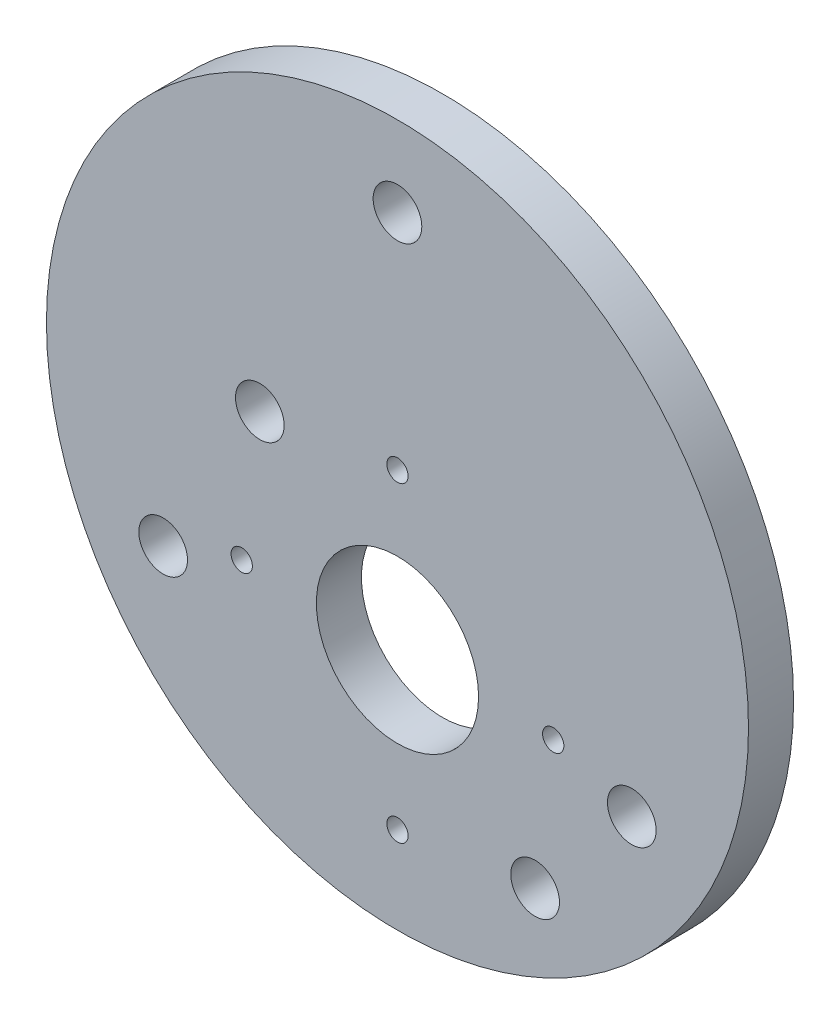
SolidWorks part; units mm, degrees
ref_plane "Front Plane" through (0, 0, 0) normal (0, 0, 1) x (1, 0, 0)
ref_plane "Top Plane" through (0, 0, 0) normal (0, 1, 0) x (1, 0, 0)
ref_plane "Right Plane" through (0, 0, 0) normal (1, 0, 0) x (0, 0, -1)
sketch "Sketch1" plane through (0, 0, 0) normal (0, 0, 1) x (1, 0, 0)
  circle A0 centre (0, 0) radius 49.4665
  dimension "D1" = 98.933
extrude "Boss-Extrude1" add sketch "Sketch1" along normal blind 6.35
sketch "Sketch2" plane through (0, 0, 6.35) normal (0, 0, 1) x (1, 0, 0)
  line L0 (0, -37.1877) -> (0, 6.7077) construction
  line L1 (-21.9477, -15.24) -> (0, 6.7077)
  line L2 (-21.9477, -15.24) -> (0, -37.1877)
  line L3 (0, -37.1877) -> (21.9477, -15.24)
  line L4 (0, 6.7077) -> (21.9477, -15.24)
  line L5 (0, -15.24) -> (12.0918, -15.24) construction
  point P4 (0, -15.24)
  point P5 (0, 0)
  point P9 (12.0918, -15.24)
  point P10 (0, 0)
  point P11 (0, 0)
  point P12 (0, 0)
  point P13 (0, 0)
  point P14 (0, 0)
  point P15 (0, 0)
  dimension "D1" = 31.0388
  dimension "D2" = 31.0388
  dimension "D3" = 15.24
  dimension "D4" = 90
hole_wizard "M3 Screw Hole - Ø3.0mm Dowel Hole" positions "Sketch3" profile "Sketch4" hole size "Ø3.0" standard "ANSI Metric" end condition through all
sketch "Sketch3" plane through (0, 0, 6.35) normal (0, 0, 1) x (1, 0, 0)
  point P0 (0, 6.7077)
  point P3 (-21.9477, -15.24)
  point P6 (0, -37.1877)
  point P9 (21.9477, -15.24)
sketch "Sketch4" plane through (0, 6.7077, 6.35) normal (1, 0, 0) x (0, -1, 0)
  line L0 (0, 0) -> (0, 6.35)
  line L1 (0, 6.35) -> (1.5, 6.35)
  line L2 (1.5, 6.35) -> (1.5, 0)
  line L5 (1.5, 0) -> (0, 0)
  line L11 (0, -6.35) -> (0, 107.95) construction
  dimension "Thru Hole Dia." = 3
  dimension "Thru Hole Depth" = 6.35
sketch "Sketch5" plane through (0, 0, 6.35) normal (0, 0, 1) x (1, 0, 0)
  line L0 (0, -37.1877) -> (0, 6.7077) construction
  line L1 (-29.9941, -15.24) -> (0, 14.7541)
  line L2 (-29.9941, -15.24) -> (0, -45.2341)
  line L3 (0, -45.2341) -> (29.9941, -15.24)
  line L4 (0, 14.7541) -> (29.9941, -15.24)
  line L5 (-29.9941, -15.24) -> (29.9941, -15.24) construction
  line L6 (0, -45.2341) -> (0, 14.7541) construction
  line L7 (-19.3974, 4.1574) -> (0, -15.24) construction
  line L8 (0, -15.24) -> (32.8719, -15.24) construction
  line L9 (0, -15.24) -> (19.3974, -34.6374) construction
  circle A0 centre (19.3974, -34.6374) radius 3.429
  circle A1 centre (-19.3974, 4.1574) radius 3.429
  point P0 (0, -15.24)
  point P7 (0, -15.24)
  point P14 (0, 0)
  dimension "D3" = 6.858
  dimension "D5" = 6.858
  dimension "D1" = 42.418
  dimension "D4" = 42.418
  dimension "D6" = 27.432
  dimension "D7" = 135
extrude "Cut-Extrude1" cut sketch "Sketch5" against normal through all contours A0 | A1 region at (19.3974, -34.6374, 6.35)
sketch "Sketch6" plane through (0, 0, 6.35) normal (0, 0, 1) x (1, 0, 0)
  line L0 (0, 38.1282) -> (-33.02, -19.0641) construction
  line L1 (-33.02, -19.0641) -> (33.02, -19.0641) construction
  line L2 (33.02, -19.0641) -> (0, 38.1282) construction
  line L3 (-33.02, -19.0641) -> (0, 0) construction
  line L4 (0, 0) -> (33.02, -19.0641) construction
  line L5 (0, 0) -> (0, 38.1282) construction
  circle A0 centre (0, 38.1282) radius 3.429
  circle A1 centre (-33.02, -19.0641) radius 3.429
  circle A2 centre (33.02, -19.0641) radius 3.429
  dimension "D1" = 6.858
  dimension "D2" = 66.04
  dimension "D3" = 60
  dimension "D4" = 60
extrude "Cut-Extrude2" cut sketch "Sketch6" against normal through all
sketch "Sketch7" plane through (0, 0, 6.35) normal (0, 0, 1) x (1, 0, 0)
  line L0 (0, -37.1877) -> (0, 6.7077) construction
  circle A0 centre (0, -15.24) radius 11.43
  point P4 (0, -15.24)
  dimension "D1" = 22.86
extrude "Cut-Extrude3" cut sketch "Sketch7" against normal through all
